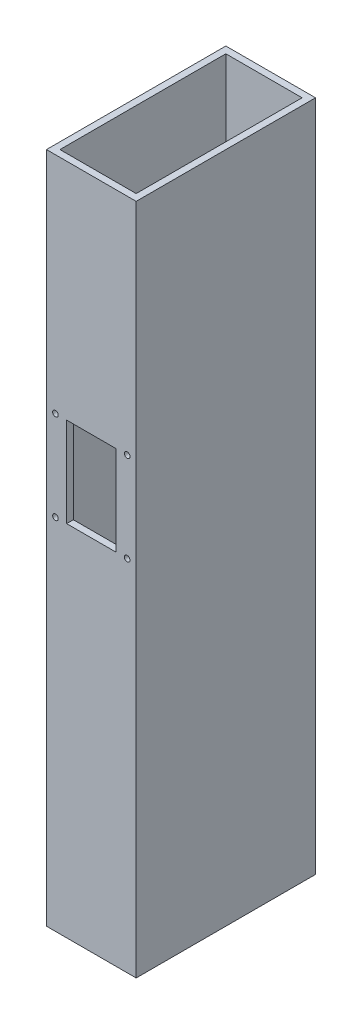
SolidWorks part; units mm, degrees
material "6061-T6 (SS)"
ref_plane "Front Plane" through (0, 0, 0) normal (0, 0, 1) x (1, 0, 0)
ref_plane "Top Plane" through (0, 0, 0) normal (0, 1, 0) x (1, 0, 0)
ref_plane "Right Plane" through (0, 0, 0) normal (1, 0, 0) x (0, 0, -1)
sketch "Sketch1" plane through (0, 0, 0) normal (0, 1, 0) x (1, 0, 0)
  line L0 (3, 3) -> (3, 77)
  line L1 (0, 0) -> (40, 0)
  line L2 (0, 0) -> (0, 80)
  line L3 (0, 80) -> (40, 80)
  line L4 (40, 0) -> (40, 80)
  line L5 (3, 77) -> (37, 77)
  line L6 (37, 3) -> (37, 77)
  line L7 (3, 3) -> (37, 3)
  dimension "D1" = 80
  dimension "D2" = 40
  dimension "D3" = 3
extrude "Boss-Extrude1" add sketch "Sketch1" along normal blind 300
sketch "Sketch2" plane through (0, 0, 0) normal (0, 0, 1) x (1, 0, 0)
  line L0 (20, 300) -> (20, 200) construction
  line L1 (9, 200) -> (31, 200)
  line L2 (9, 200) -> (9, 160)
  line L3 (9, 160) -> (31, 160)
  line L4 (31, 200) -> (31, 160)
  line L5 (0, 300) -> (40, 300) construction
  dimension "D1" = 22
  dimension "D2" = 100
  dimension "D3" = 40
extrude "Cut-Extrude1" cut sketch "Sketch2" against normal up to next
sketch "Sketch3" plane through (0, 0, 0) normal (0, 0, 1) x (1, 0, 0)
  line L0 (9, 200) -> (9, 160) construction
  line L2 (31, 160) -> (31, 200) construction
  line L3 (4, 200) -> (9, 200) construction
  point P0 (4, 200)
  point P11 (36, 200)
  point P12 (36, 160)
  point P13 (4, 160)
  dimension "D1" = 5
  dimension "D5" = 5
  dimension "D6" = 40
  dimension "D3" = 2
  dimension "D4" = 2
hole_wizard "Tap Drill for M3 Tap1" positions "Sketch3" profile "Sketch5" hole size "M3" standard "DIN" end condition up to next
sketch "Sketch5" plane through (4, 200, 0) normal (1, 0, 0) x (0, -1, 0)
  line L0 (0, 0) -> (0, 3)
  line L1 (0, 3) -> (1.25, 3)
  line L2 (1.25, 3) -> (1.25, 0)
  line L5 (1.25, 0) -> (0, 0)
  line L11 (0, -6.35) -> (0, 107.95) construction
  dimension "Thru Hole Dia." = 2.5
  dimension "Thru Hole Depth" = 3
